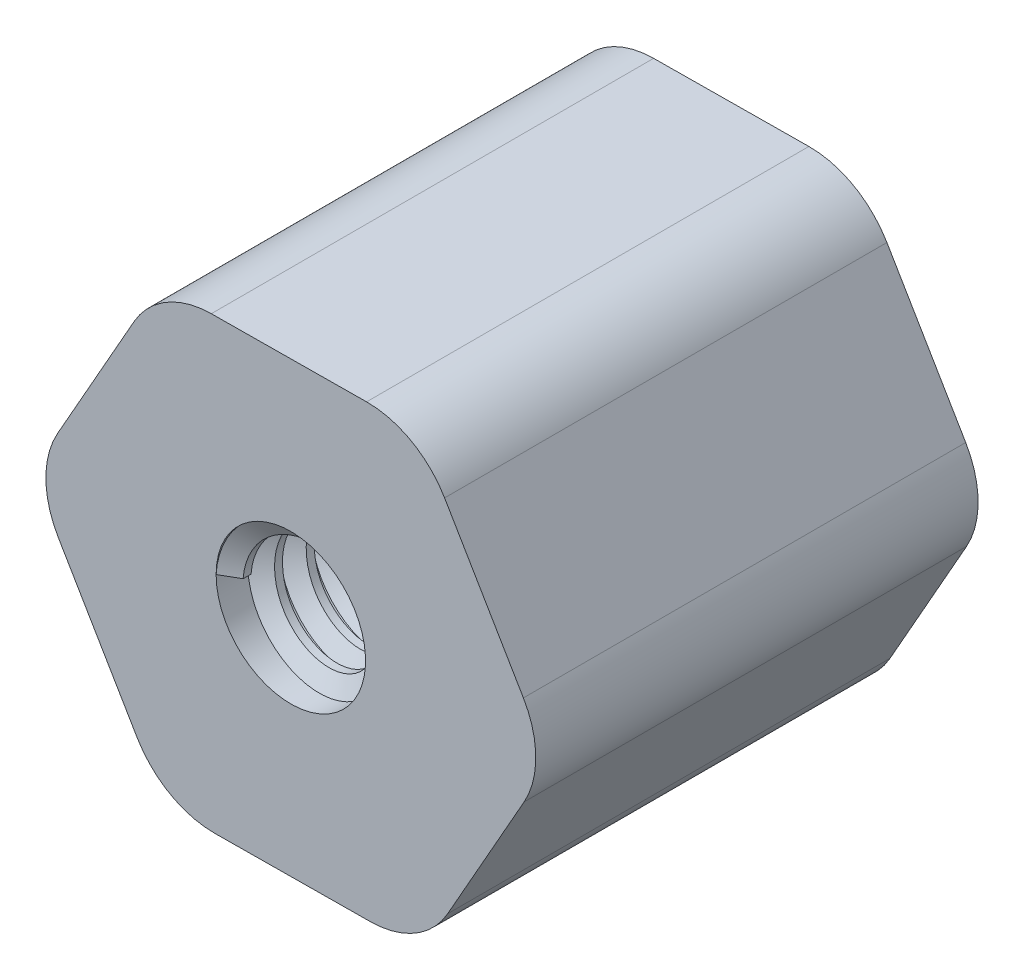
SolidWorks part; units mm, degrees
ref_plane "Alzado" through (0, 0, 0) normal (0, 0, 1) x (1, 0, 0)
ref_plane "Planta" through (0, 0, 0) normal (0, 1, 0) x (1, 0, 0)
ref_plane "Vista lateral" through (0, 0, 0) normal (1, 0, 0) x (0, 0, -1)
sketch "Croquis1" plane through (0, 0, 0) normal (0, 0, 1) x (1, 0, 0)
  line L1 (2.5343, 7.5218) -> (-2.6617, 7.4777)
  line L2 (-5.2469, 5.9556) -> (-7.8067, 1.4337)
  line L3 (-7.7812, -1.5662) -> (-5.145, -6.0439)
  line L4 (-2.5343, -7.5218) -> (2.6617, -7.4777)
  line L5 (5.2469, -5.9556) -> (7.8067, -1.4337)
  line L6 (7.7812, 1.5662) -> (5.145, 6.0439)
  circle A0 centre (0, 0) radius 2.5
  circle A1 centre (0, 0) radius 7.5 construction
  arc A2 (-2.6617, 7.4777) -> (-5.2469, 5.9556) centre (-2.6362, 4.4778) ccw
  arc A3 (2.5343, 7.5218) -> (5.145, 6.0439) centre (2.5598, 4.5219) cw
  arc A4 (7.8067, -1.4337) -> (7.7812, 1.5662) centre (5.196, 0.0441) ccw
  arc A5 (2.6617, -7.4777) -> (5.2469, -5.9556) centre (2.6362, -4.4778) ccw
  arc A6 (-5.145, -6.0439) -> (-2.5343, -7.5218) centre (-2.5598, -4.5219) ccw
  arc A7 (-7.8067, 1.4337) -> (-7.7812, -1.5662) centre (-5.196, -0.0441) ccw
  dimension "D1" = 15
  dimension "D2" = 5
  dimension "D3" = 3
extrude "Saliente-Extruir1" add sketch "Croquis1" along normal blind 14.8
thread "Rosca1" pitch 1.0583 method extrude profile "Perfil de rosca2" start angle 0, offset 0, length 13.8, pitch 1.0583, diameter 5
ref_plane "Plano2" through (-2.5, 0, 14.8) normal (0, -1, 0) x (-1, 0, 0)
sketch "Perfil de rosca2" plane through (-2.5, 0, 14.8) normal (0, -1, 0) x (-1, 0, 0)
  line L0 (0, 0) -> (0, 1.0583) construction
  line L11 (0, 0) -> (0, 0.926)
  line L12 (0, 0.926) -> (-0.5728, 0.5953)
  line L13 (-0.5728, 0.5953) -> (-0.5728, 0.3307)
  line L15 (-0.5728, 0.3307) -> (0, 0)
  line L17 (-0.5728, 0.463) -> (0, 0.463) construction
  point P2 (0, 0)
  dimension "Pitch" = 1.0583
  dimension "Profile_Angle" = 60
  dimension "Profile_Land" = 0.2646
  dimension "Profile_Height" = 0.5728
